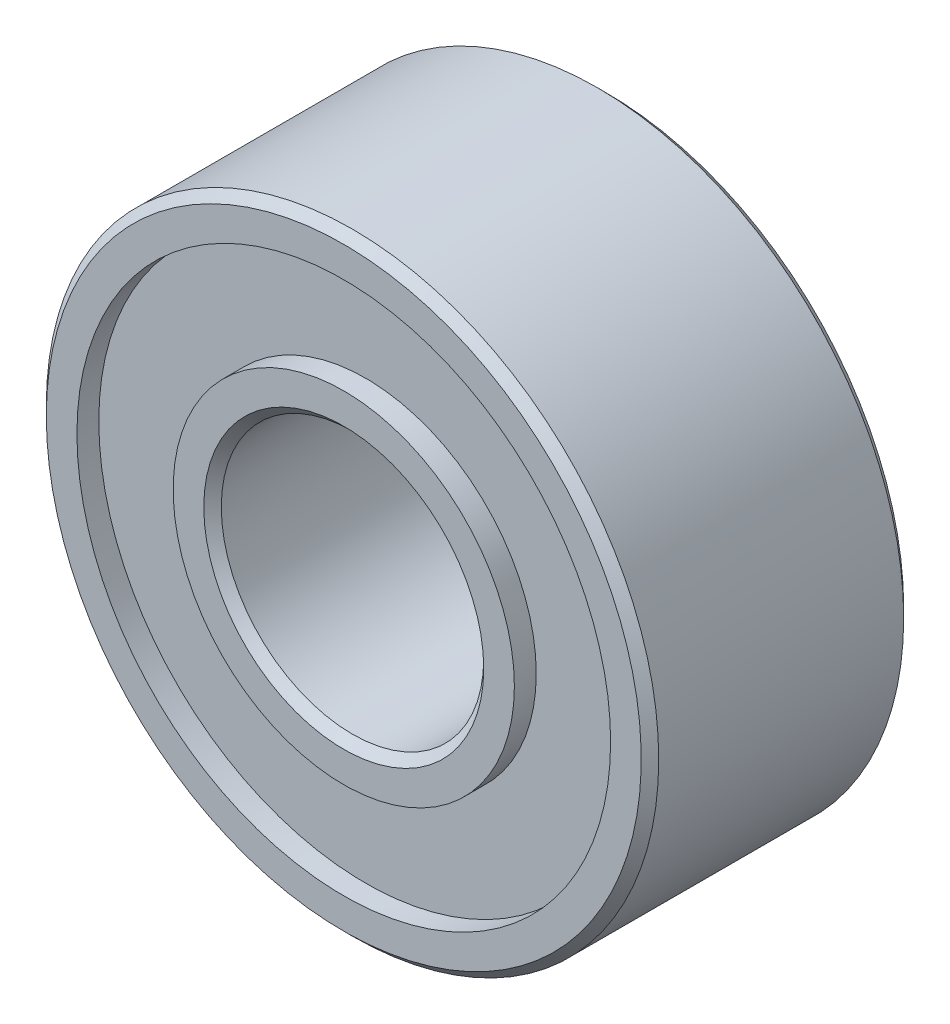
SolidWorks part; units mm, degrees
ref_plane "Ebene vorne" through (0, 0, 0) normal (0, 0, 1) x (1, 0, 0)
ref_plane "Ebene oben" through (0, 0, 0) normal (0, 1, 0) x (1, 0, 0)
ref_plane "Ebene rechts" through (0, 0, 0) normal (1, 0, 0) x (0, 0, -1)
sketch "Skizze2" plane through (0, 0, 0) normal (1, 0, 0) x (0, 0, -1)
  line L0 (-11.8458, 0) -> (13.4965, 0) construction
  line L1 (0, 16.288) -> (0, -14.1034) construction
  line L2 (-1.5, 1.5) -> (1.5, 1.5)
  line L3 (1.5, 1.5) -> (1.5, 1.95)
  line L4 (1.5, 1.95) -> (1.25, 1.95)
  line L5 (1.25, 1.95) -> (1.25, 3.05)
  line L6 (1.25, 3.05) -> (1.5, 3.05)
  line L7 (1.5, 3.05) -> (1.5, 3.5)
  line L8 (1.5, 3.5) -> (-1.5, 3.5)
  line L9 (-1.5, 3.05) -> (-1.5, 3.5)
  line L10 (-1.25, 3.05) -> (-1.5, 3.05)
  line L11 (-1.25, 1.95) -> (-1.25, 3.05)
  line L12 (-1.5, 1.95) -> (-1.25, 1.95)
  line L13 (-1.5, 1.5) -> (-1.5, 1.95)
  point P5 (0, 3.5)
  point P19 (0, 1.5)
  dimension "D1" = 3
  dimension "D2" = 7
  dimension "D3" = 3
  dimension "D4" = 3.9
  dimension "D5" = 6.1
  dimension "D6" = 2.5
revolve "Rotation1" add sketch "Skizze2" angle 360 about L0
ref_axis "Achse1" through (0, 0, -1.65) along (0, 0, 1)
chamfer "Fase1" distance 0.1 angle 45 4 edges at (1.5, 0, -1.5) (1.5, 0, 1.5) (3.5, 0, -1.5) (3.5, 0, 1.5)
